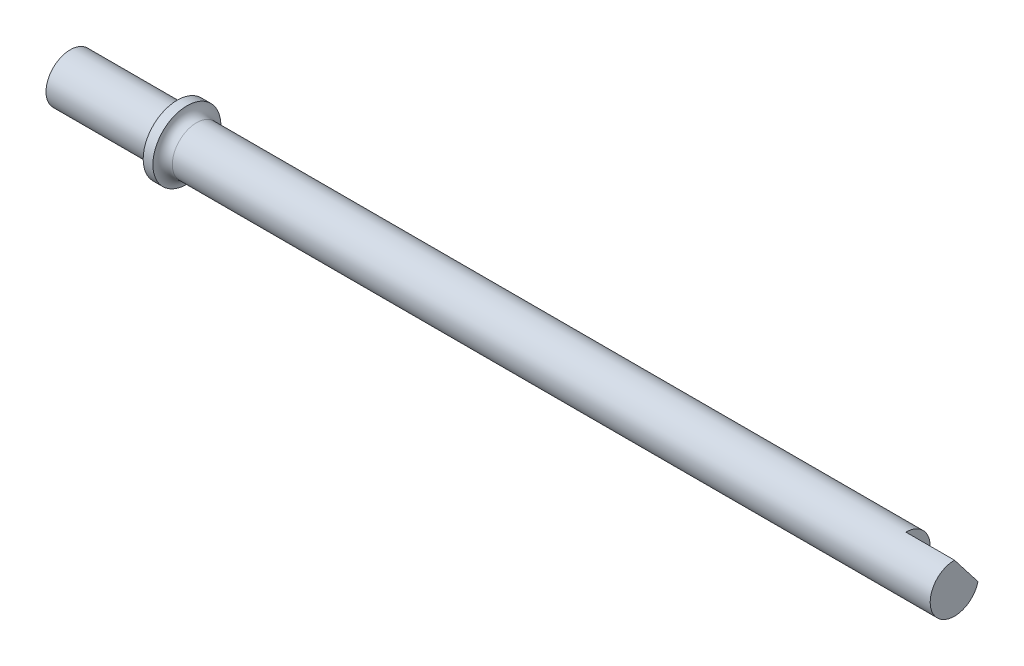
SolidWorks part; units mm, degrees
ref_plane "Plan de face" through (0, 0, 0) normal (0, 0, 1) x (1, 0, 0)
ref_plane "Plan de dessus" through (0, 0, 0) normal (0, 1, 0) x (1, 0, 0)
ref_plane "Plan de droite" through (0, 0, 0) normal (1, 0, 0) x (0, 0, -1)
sketch "Esquisse1" plane through (0, 0, 0) normal (0, 0, 1) x (1, 0, 0)
  line L0 (-22.3968, 0) -> (243.7185, 0) construction
  line L1 (0, 0) -> (146, 0)
  line L2 (0, 0) -> (0, 5)
  line L3 (0, 5) -> (146, 5)
  line L4 (146, 0) -> (146, 5)
  line L9 (22, 5) -> (24, 5)
  line L10 (22, 5) -> (22, 7)
  line L11 (22, 7) -> (24, 7)
  line L12 (24, 5) -> (24, 7)
  line L14 (146, 5) -> (182, 5)
  line L15 (146, 5) -> (146, 0)
  line L16 (146, 0) -> (182, 0)
  line L17 (182, 5) -> (182, 0)
  dimension "D1" = 5
  dimension "D2" = 146
  dimension "D3" = 36
  dimension "D6" = 2
  dimension "D7" = 2
  dimension "D8" = 22
revolve "Révolution1" add sketch "Esquisse1" angle 360 about L0 region at (164, 2.5, 0) region at (23, 6, 0)
fillet "Congé1" radius 2 1 edges at (24, 0, 5)
ref_plane "Plan1" through (0, -5, 0) normal (0, -1, 0) x (-1, 0, 0)
sketch "Esquisse6" plane through (0, -5, 0) normal (0, -1, 0) x (-1, 0, 0)
  line L0 (0, -5) -> (0, 5) construction
  circle A0 centre (-7.5, 0) radius 2
  dimension "D1" = 7.5
extrude "Enlèv. mat.-Extru.2" cut sketch "Esquisse6" against normal blind 5
sketch "Esquisse7" plane through (0, 0, 0) normal (-1, 0, 0) x (0, 0, 1)
  circle A0 centre (0, 0) radius 3
  dimension "D1" = 6
extrude "Enlèv. mat.-Extru.3" cut sketch "Esquisse7" against normal blind 16.3 contours A0
sketch "Esquisse8" plane through (182, 0, 0) normal (1, 0, 0) x (0, 0, -1)
  line L0 (0, 5) -> (4.8432, -1.2422)
  circle A0 centre (0, 0) radius 5 construction
  circle A1 centre (0, 0) radius 5 construction
extrude "Enlèv. mat.-Extru.4" cut sketch "Esquisse8" against normal blind 10 and the other way through all
